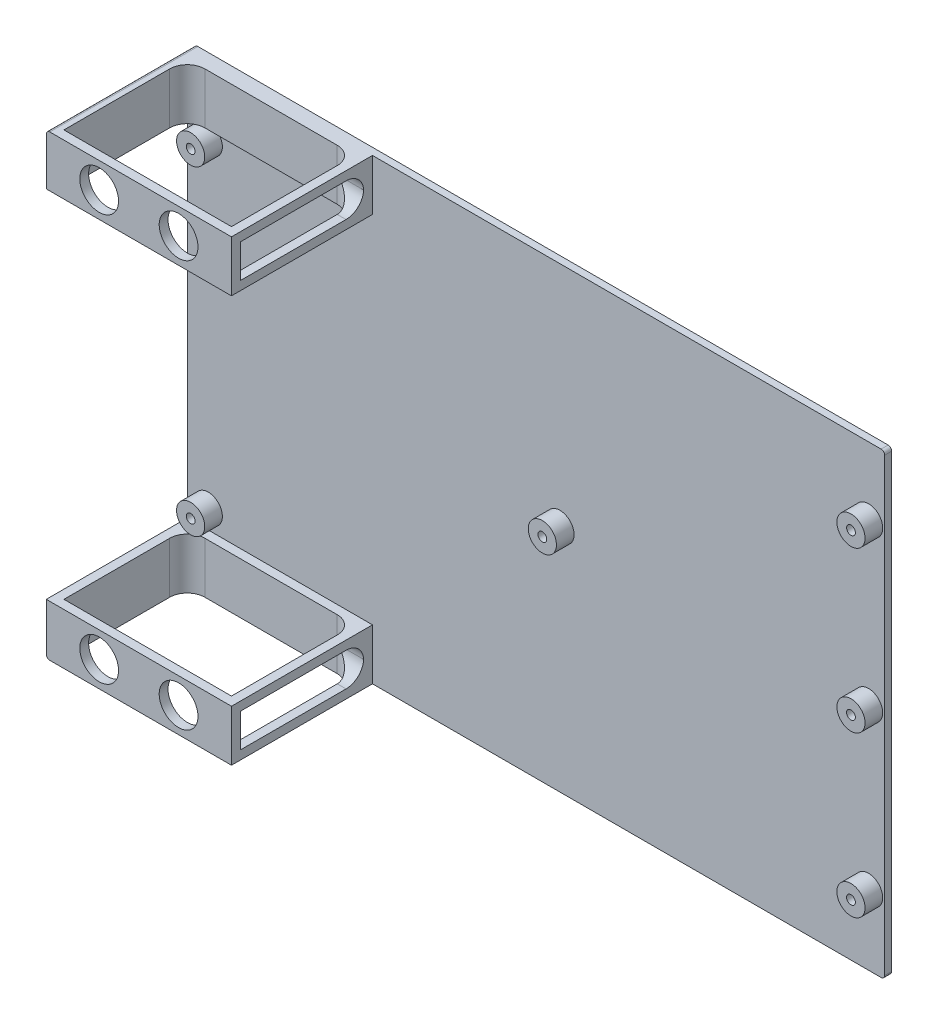
SolidWorks part; units mm, degrees
ref_plane "Front Plane" through (0, 0, 0) normal (0, 0, 1) x (1, 0, 0)
ref_plane "Top Plane" through (0, 0, 0) normal (0, 1, 0) x (1, 0, 0)
ref_plane "Right Plane" through (0, 0, 0) normal (1, 0, 0) x (0, 0, -1)
ref_plane "Plane1" through (0, 0, 134.4995) normal (0, 0, -1) x (-1, 0, 0)
sketch "Sketch2" plane through (0, 0, 134.4995) normal (0, 0, -1) x (-1, 0, 0)
  line L0 (9.9552, 158.975) -> (-182.3228, 158.975) construction
  line L1 (-185.1008, 44.153) -> (12.7332, 44.153)
  line L2 (-185.1008, 44.153) -> (-185.1008, 173.975)
  line L3 (-185.1008, 173.975) -> (12.7332, 173.975)
  line L4 (12.7332, 44.153) -> (12.7332, 173.975)
  line L5 (-182.3228, 59.153) -> (9.9552, 59.153) construction
  line L6 (11.7332, 60.931) -> (11.7332, 157.197) construction
  line L7 (-184.1008, 157.197) -> (-184.1008, 60.931) construction
  dimension "D1" = 15
  dimension "D2" = 15
  dimension "D3" = 1
  dimension "D4" = 1
extrude "Boss-Extrude1" add sketch "Sketch2" along normal blind 2
sketch "Sketch3" plane through (0, 0, 134.4995) normal (0, 0, 1) x (1, 0, 0)
  circle A0 centre (180.5448, 154.784) radius 4
  circle A1 centre (180.5448, 109.3815) radius 4
  circle A2 centre (180.5448, 63.979) radius 4
  circle A3 centre (92.991, 109.3815) radius 4
  circle A4 centre (-6.7802, 154.784) radius 4
  circle A5 centre (-6.7802, 63.979) radius 4
  dimension "D1" = 8
  dimension "D2" = 8
  dimension "D3" = 8
  dimension "D4" = 8
  dimension "D5" = 8
  dimension "D6" = 8
extrude "Boss-Extrude2" add sketch "Sketch3" along normal up to surface (5 mm away)
hole_wizard "Tap Drill for M3x0.5 Tap1" positions "Sketch4" profile "Sketch5" hole size "M3x0.5" standard "ANSI Metric" end condition through all
sketch "Sketch4" plane through (0, 0, 139.4995) normal (0, 0, 1) x (1, 0, 0)
  point P0 (180.5448, 154.784)
  point P3 (180.5448, 109.3815)
  point P6 (180.5448, 63.979)
  point P9 (92.991, 109.3815)
  point P12 (-6.7802, 63.979)
  point P15 (-6.7802, 154.784)
sketch "Sketch5" plane through (180.5448, 154.784, 139.4995) normal (1, 0, 0) x (0, -1, 0)
  line L0 (0, 0) -> (0, 7)
  line L1 (0, 7) -> (1.25, 7)
  line L2 (1.25, 7) -> (1.25, 0)
  line L5 (1.25, 0) -> (0, 0)
  line L11 (0, -6.35) -> (0, 107.95) construction
  dimension "Thru Hole Dia." = 2.5
  dimension "Thru Hole Depth" = 7
ref_plane "Plane2" through (-12.7332, 173.975, 134.4995) normal (1, 0, 0) x (0, 0, -1)
sketch "Sketch8" plane through (0, 0, 134.4995) normal (0, 0, 1) x (1, 0, 0)
  line L1 (-12.7332, 173.975) -> (35.0345, 173.975)
  line L2 (-12.7332, 173.975) -> (-12.7332, 159.267)
  line L3 (-12.7332, 159.267) -> (35.0345, 159.267)
  line L4 (35.0345, 173.975) -> (35.0345, 159.267)
sketch "Sketch9" plane through (0, 0, 134.4995) normal (0, 0, 1) x (1, 0, 0)
  line L1 (-12.7332, 173.975) -> (39.7987, 173.975)
  line L2 (-12.7332, 173.975) -> (-12.7332, 159.475)
  line L3 (-12.7332, 159.475) -> (39.7987, 159.475)
  line L4 (39.7987, 173.975) -> (39.7987, 159.475)
  dimension "D1" = 14.5
extrude "Boss-Extrude3" add sketch "Sketch9" along normal blind 40
sketch "Sketch11" plane through (0, 0, 174.4995) normal (0, 0, 1) x (1, 0, 0)
  line L0 (39.7987, 173.975) -> (-12.7332, 173.975) construction
  line L1 (37.2987, 173.975) -> (-10.2332, 173.975)
  line L2 (37.2987, 173.975) -> (37.2987, 159.475)
  line L3 (37.2987, 159.475) -> (-10.2332, 159.475)
  line L4 (-10.2332, 173.975) -> (-10.2332, 159.475)
  line L5 (-12.7332, 159.475) -> (39.7987, 159.475) construction
  line L6 (39.7987, 159.475) -> (39.7987, 173.975) construction
  line L7 (39.7987, 161.975) -> (-12.7332, 161.975)
  line L8 (39.7987, 161.975) -> (39.7987, 171.475)
  line L9 (39.7987, 171.475) -> (-12.7332, 171.475)
  line L10 (-12.7332, 161.975) -> (-12.7332, 171.475)
  line L11 (-12.7332, 173.975) -> (-12.7332, 159.475) construction
  line M6 (-12.7332, 159.475) -> (39.7987, 159.475)
  line M7 (39.7987, 159.475) -> (39.7987, 173.975)
  line M8 (39.7987, 173.975) -> (-12.7332, 173.975)
  dimension "D1" = 2.5
  dimension "D2" = 2.5
  dimension "D3" = 2.5
  dimension "D4" = 2.5
extrude "Cut-Extrude1" cut sketch "Sketch11" against normal offset from surface (35 mm away) 2.5 from offset 2.5 contours L2 L9 L4 L7 | L2 L7 L4 M6 | L9 L2 L4 M8 | L9 L2 L7 M7 region at (13.5328, 172.725, 174.4995) region at (38.5487, 166.725, 174.4995) region at (13.5328, 166.725, 174.4995) region at (13.5328, 160.725, 174.4995) up to face at (-2.7802, 63.979, 134.4995) offset against normal yes
sketch "Sketch12" plane through (0, 0, 174.4995) normal (0, 0, 1) x (1, 0, 0)
  line L0 (39.7987, 159.475) -> (39.7987, 173.975) construction
  line L1 (-12.7332, 173.975) -> (-12.7332, 159.475) construction
  circle A0 centre (2.2668, 166.725) radius 5.5
  circle A1 centre (24.7987, 166.725) radius 5.5
  dimension "D3" = 11
  dimension "D4" = 11
  dimension "D1" = 15
  dimension "D2" = 15
extrude "Cut-Extrude2" cut sketch "Sketch12" against normal up to next
fillet "Fillet1" radius 5 5 edges at (-10.2332, 166.725, 136.9995) (38.5487, 171.475, 136.9995) (37.2987, 172.725, 136.9995) (38.5487, 161.975, 136.9995) (37.2987, 160.725, 136.9995)
ref_plane "Plane3" through (0, 109.064, 0) normal (0, 1, 0) x (1, 0, 0)
mirror "Mirror1" about plane through (0, 109.064, 0) normal (0, 1, 0) of "Boss-Extrude3", "Cut-Extrude1", "Cut-Extrude2", "Fillet1"
fillet "Fillet2" radius 1 4 edges at (185.1008, 173.975, 133.4995) (185.1008, 44.153, 133.4995) (-12.7332, 44.153, 153.4995) (-12.7332, 173.975, 153.4995)
